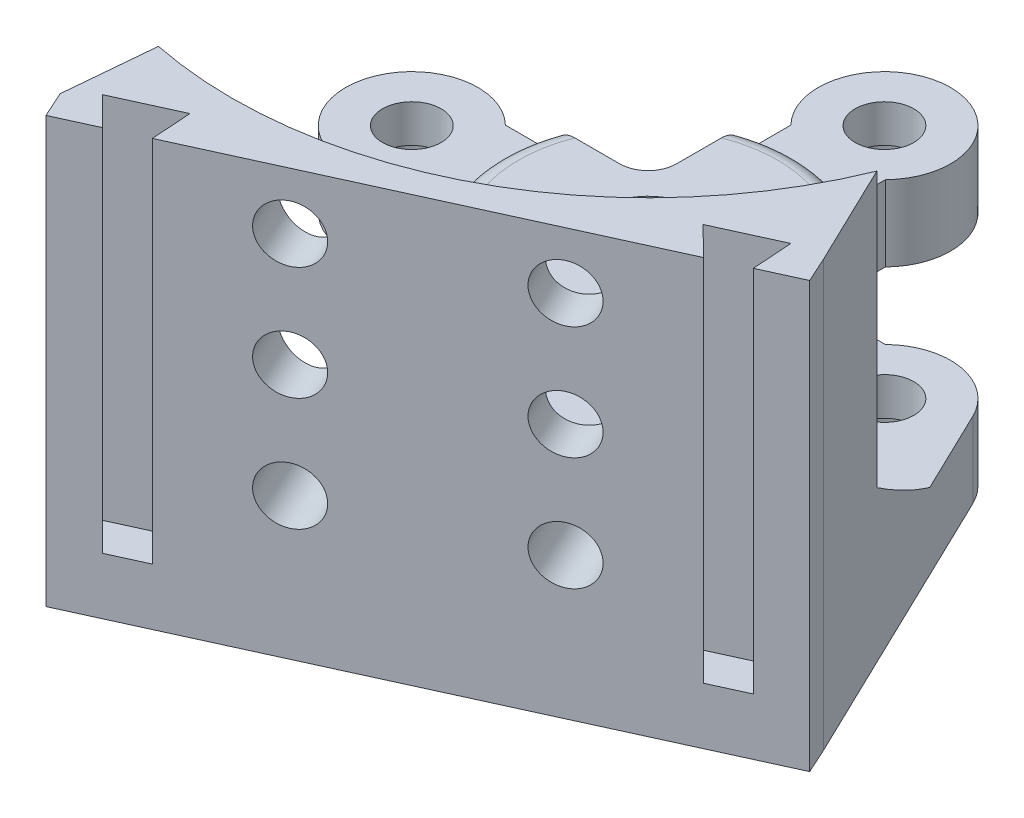
SolidWorks part; units mm, degrees
material "Nylon 6/10"
ref_plane "Front Plane" through (0, 0, 0) normal (0, 0, 1) x (1, 0, 0)
ref_plane "Top Plane" through (0, 0, 0) normal (0, 1, 0) x (1, 0, 0)
ref_plane "Right Plane" through (0, 0, 0) normal (1, 0, 0) x (0, 0, -1)
sketch "Sketch1" plane through (0, 0, 0) normal (0, 1, 0) x (1, 0, 0)
  line L0 (-5, 5) -> (-5, 25)
  line L1 (-25, -5) -> (-5, -5)
  line L2 (-25, -5) -> (-25, 5)
  line L3 (-25, 5) -> (-5, 5)
  line L4 (25, -5) -> (25, 5)
  line L5 (-25, -5) -> (25, 5) construction
  line L6 (-25, 5) -> (25, -5) construction
  line L7 (-5, -25) -> (5, -25)
  line L8 (-5, -25) -> (-5, -5)
  line L9 (-5, 25) -> (5, 25)
  line L10 (5, -25) -> (5, -5)
  line L11 (-5, -25) -> (5, 25) construction
  line L12 (-5, 25) -> (5, -25) construction
  line L13 (5, 5) -> (25, 5)
  line L14 (5, 5) -> (5, 25)
  line L15 (5, -5) -> (25, -5)
  point P0 (0, 0)
  point P6 (0, 0)
  dimension "D1" = 10
  dimension "D2" = 10
  dimension "D3" = 50
  dimension "D4" = 50
extrude "Boss-Extrude1" add sketch "Sketch1" along normal blind 8
sketch "Sketch2" plane through (0, 8, 0) normal (0, 1, 0) x (1, 0, 0)
  line L0 (25, -5) -> (25, 5) construction
  circle A0 centre (25, 0) radius 7
  circle A1 centre (0, -25) radius 7
  circle A2 centre (-25, 0) radius 7
  circle A3 centre (0, 25) radius 7
  point P13 (0, 0)
  dimension "D1" = 14
  dimension "D2" = 4
extrude "Boss-Extrude2" add sketch "Sketch2" against normal up to surface (8 mm away) up to face at (0, 0, 0)
sketch "Sketch3" plane through (0, 8, 0) normal (0, 1, 0) x (1, 0, 0)
  circle A0 centre (25, 0) radius 3.1
  circle A1 centre (0, -25) radius 3.1
  circle A2 centre (-25, 0) radius 3.1
  circle A3 centre (0, 25) radius 3.1
  point P12 (0, 0)
  dimension "D1" = 6.2
  dimension "D2" = 4
extrude "Cut-Extrude1" cut sketch "Sketch3" against normal up to surface (8 mm away) up to face at (0, 0, 0)
sketch "Sketch4" plane through (0, 0, 0) normal (0, 1, 0) x (1, 0, 0)
  circle A0 centre (25, 0) radius 5.05
  circle A1 centre (0, -25) radius 5.05
  circle A2 centre (-25, 0) radius 5.05
  circle A3 centre (0, 25) radius 5.05
  point P12 (0, 0)
  dimension "D1" = 10.1
  dimension "D2" = 4
extrude "Cut-Extrude4" cut sketch "Sketch4" along normal blind 4
sketch "Sketch5" plane through (0, 8, 0) normal (0, 1, 0) x (1, 0, 0)
  line L8 (5, 5) -> (5, 20.101)
  line L9 (-5, 20.101) -> (-5, 5)
  line L10 (-5, 5) -> (-20.101, 5)
  line L11 (-20.101, -5) -> (-5, -5)
  line L12 (-5, -5) -> (-5, -20.101)
  line L13 (5, -20.101) -> (5, -5)
  line L14 (5, -5) -> (20.101, -5)
  line L15 (20.101, 5) -> (5, 5)
  line L16 (5, 5) -> (5, 14.8825)
  line L17 (-5, 14.8825) -> (-5, 5)
  line L18 (-5, 5) -> (-14.8825, 5)
  line L19 (-14.8825, -5) -> (-5, -5)
  line L20 (-5, -5) -> (-5, -14.8825)
  line L21 (5, -14.8825) -> (5, -5)
  line L22 (5, -5) -> (14.8825, -5)
  line L23 (14.8825, 5) -> (5, 5)
  arc A0 (-14.8825, 5) -> (-14.8825, -5) centre (0, 0) ccw
  arc A1 (5, 14.8825) -> (-5, 14.8825) centre (0, 0) ccw
  arc A2 (14.8825, -5) -> (14.8825, 5) centre (0, 0) ccw
  arc A3 (-5, -14.8825) -> (5, -14.8825) centre (0, 0) ccw
  arc A5 (5, 20.101) -> (-5, 20.101) centre (0, 25) ccw
  arc A6 (-20.101, 5) -> (-20.101, -5) centre (-25, 0) ccw
  arc A7 (-5, -20.101) -> (5, -20.101) centre (0, -25) ccw
  arc A8 (20.101, -5) -> (20.101, 5) centre (25, 0) ccw
  dimension "D1" = 31.4
  dimension "D2" = 0
extrude "Boss-Extrude3" add sketch "Sketch5" along normal blind 2.5
sketch "Sketch6" plane through (0, 0, 0) normal (0, -1, 0) x (1, 0, 0)
  line L1 (-8.8, -8.8) -> (8.8, -8.8)
  line L2 (-8.8, -8.8) -> (-8.8, 8.8)
  line L3 (-8.8, 8.8) -> (8.8, 8.8)
  line L4 (8.8, -8.8) -> (8.8, 8.8)
  line L5 (-8.8, -8.8) -> (8.8, 8.8) construction
  line L6 (-8.8, 8.8) -> (8.8, -8.8) construction
  point P0 (0, 0)
  dimension "D1" = 17.6
  dimension "D2" = 90
extrude "Boss-Extrude4" add sketch "Sketch6" along normal blind 9.8
sketch "Sketch7" plane through (0, 10.5, 0) normal (0, 1, 0) x (1, 0, 0)
  circle A0 centre (0, 0) radius 5
  dimension "D1" = 10
extrude "Cut-Extrude5" cut sketch "Sketch7" against normal up to surface (20.3 mm away) up to face at (0, -9.8, 0)
fillet "Fillet1" radius 2 4 edges at (15.7, 10.5, 0) (0, 10.5, 15.7) (-15.7, 10.5, 0) (0, 10.5, -15.7)
sketch "Sketch8" plane through (0, 0, 0) normal (0, -1, 0) x (1, 0, 0)
  line L0 (-16.8381, 40.6507) -> (0, 0) construction
  line L1 (0, 0) -> (40.6507, 16.8381) construction
  line L2 (0, 0) -> (44, 0) construction
  line L3 (-9.5299, 52.6824) -> (45.9886, 27.4099)
  line L4 (18.2293, 40.0461) -> (0, 0) construction
  line L6 (8.8, 5) -> (20.101, 5) construction
  line L7 (5, 5) -> (8.8, 5) construction
  line L8 (5, 8.8) -> (5, 5) construction
  line L9 (5, 20.101) -> (5, 8.8) construction
  line L11 (8.8, 5) -> (20.101, 5)
  line L12 (5, 5) -> (8.8, 5)
  line L13 (5, 8.8) -> (5, 5)
  line L14 (5, 20.101) -> (5, 8.8)
  line L15 (-9.5299, 52.6824) -> (-6.9716, 24.37)
  line L18 (45.9886, 27.4099) -> (31.3052, -3.0404)
  circle A0 centre (0, 0) radius 44 construction
  arc A1 (-16.8381, 40.6507) -> (40.6507, 16.8381) centre (0, 0) cw construction
  arc A2 (20.101, -5) -> (20.101, 5) centre (25, 0) ccw construction
  arc A3 (5, 20.101) -> (-5, 20.101) centre (0, 25) ccw construction
  arc A4 (31.3052, -3.0404) -> (20.101, 5) centre (25, 0) ccw
  arc A5 (5, 20.101) -> (-6.9716, 24.37) centre (0, 25) ccw
  dimension "D1" = 88
  dimension "D2" = 90
  dimension "D3" = 22.5
  dimension "D4" = 61
extrude "Boss-Extrude5" add sketch "Sketch8" against normal up to surface (8 mm away) up to face at (-20.6709, 8, 0)
sketch "Sketch10" plane through (18.2293, 0, 40.0461) normal (0.4143, 0, 0.9101) x (0.9101, 0, -0.4143)
  line L0 (30.5, 8) -> (30.5, 0) construction
  line L1 (-30.5, 0) -> (30.5, 0)
  line L2 (-30.5, 0) -> (-30.5, 45)
  line L3 (-30.5, 45) -> (30.5, 45)
  line L4 (30.5, 0) -> (30.5, 45)
  dimension "D1" = 45
extrude "Boss-Extrude6" add sketch "Sketch10" along normal blind 3
sketch "Sketch11" plane through (0, 8, 0) normal (0, 1, 0) x (1, 0, 0)
  line L0 (31.3052, 3.0404) -> (45.9886, -27.4099) construction
  line L1 (-9.5299, -52.6824) -> (-6.9716, -24.37) construction
  line L2 (40.7611, -16.5691) -> (45.9886, -27.4099)
  line L3 (-9.5299, -52.6824) -> (-8.6675, -43.1379)
  line L4 (45.9886, -27.4099) -> (-9.5299, -52.6824) construction
  line L5 (45.9886, -27.4099) -> (-9.5299, -52.6824)
  circle A0 centre (0, 0) radius 44 construction
  arc A1 (40.7611, -16.5691) -> (-8.6675, -43.1379) centre (0, 0) cw
  line M6 (-6.9716, -24.37) -> (-9.5299, -52.6824)
  line M7 (-9.5299, -52.6824) -> (45.9886, -27.4099)
  line M8 (45.9886, -27.4099) -> (31.3052, 3.0404)
  dimension "D1" = 88
extrude "Boss-Extrude7" add sketch "Sketch11" along normal up to surface (37 mm away) contours A1 M7 M6 | A1 L5 M8 region at (-2.1231, 8, 46.5367) region at (37.7078, 8, 27.3197) up to face at (18.8508, 45, 41.4113)
sketch "Sketch12" plane through (0, 45, 0) normal (0, 1, 0) x (1, 0, 0)
  line L0 (19.4722, -42.7765) -> (10.8877, -23.9181) construction
  line L1 (47.2315, -30.1403) -> (-8.287, -55.4128) construction
  line L2 (-4.1914, -53.5484) -> (-7.2138, -50.5293)
  line L3 (-7.2138, -50.5293) -> (-0.8428, -47.6292)
  line L4 (-0.8428, -47.6292) -> (-0.5508, -51.8912)
  line L5 (-0.5508, -51.8912) -> (-4.1914, -53.5484)
  line L6 (-2.3711, -52.7198) -> (-5.4292, -46.0018) construction
  line L7 (41.3156, -32.8333) -> (38.2575, -26.1153) construction
  line L8 (39.4953, -33.6619) -> (43.1359, -32.0047)
  line L9 (36.4729, -30.6428) -> (39.4953, -33.6619)
  line L10 (42.8438, -27.7427) -> (36.4729, -30.6428)
  line L11 (43.1359, -32.0047) -> (42.8438, -27.7427)
  point P10 (-0.6976, -51.958)
  point P11 (-1.5391, -47.7212)
  point P12 (0, 0)
  dimension "D1" = 24
  dimension "D3" = 7
  dimension "D2" = 4
  dimension "D4" = 3.5
  dimension "D5" = 4
extrude "Cut-Extrude6" cut sketch "Sketch12" against normal offset from surface (39 mm away) 6 up to face at (11.5974, 0, 19.2391)
fillet "Fillet3" radius 3 3 edges at (5, 5.25, -5) (-5, 5.25, -5) (-5, 5.25, 5)
sketch "Sketch13" plane through (19.4722, 0, 42.7765) normal (0.4143, 0, 0.9101) x (0.9101, 0, -0.4143)
  line L0 (0, 44.5069) -> (0, 0) construction
  line L1 (22, 45) -> (-22, 45) construction
  circle A0 centre (-11, 39) radius 3
  circle A1 centre (-11, 27) radius 3
  circle A2 centre (-11, 15) radius 3
  circle A3 centre (11, 15) radius 3
  circle A4 centre (11, 27) radius 3
  circle A5 centre (11, 39) radius 3
  dimension "D1" = 6
  dimension "D2" = 11
  dimension "D3" = 6
  dimension "D4" = 3
extrude "Cut-Extrude7" cut sketch "Sketch13" against normal up to surface (3.7334 mm away) up to face at (18.4394, 26.5, 34.3047)
chamfer "Chamfer1" distance 8 angle 45 1 edges at (20.8321, 8, 38.756)
equation "\"D3@Sketch2\"= 50 - \"D2@Sketch2\""
